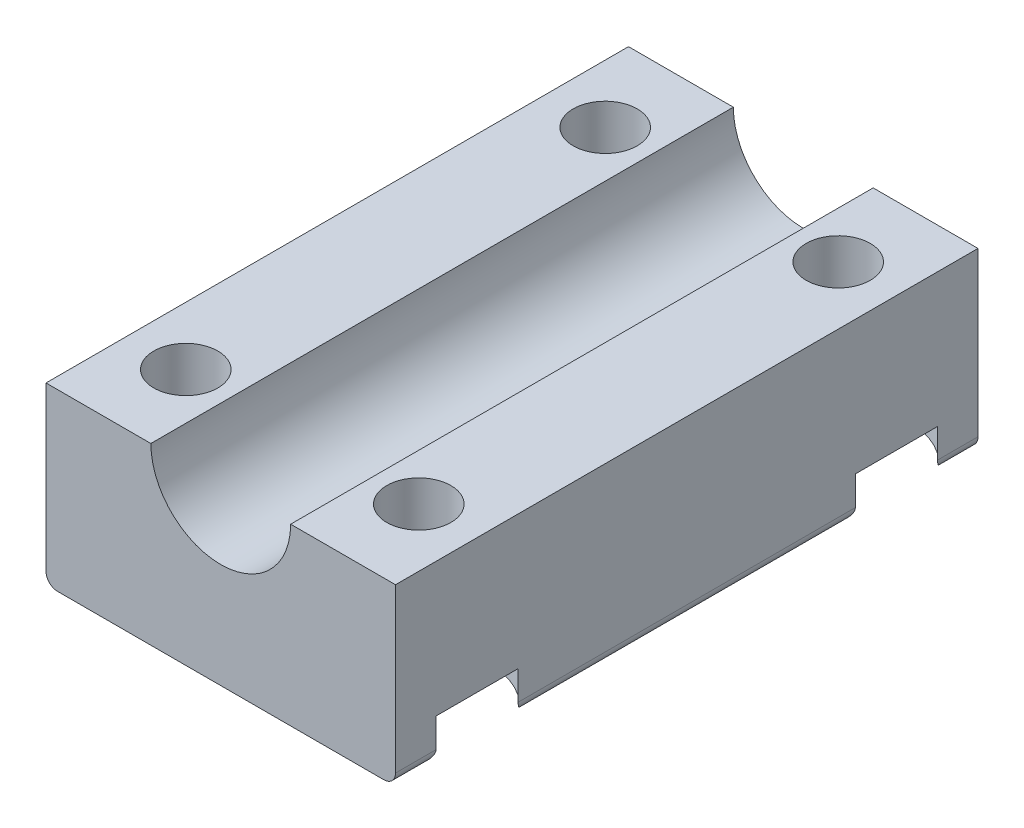
SolidWorks part; units mm, degrees
material "Alloy Steel"
ref_plane "Front Plane" through (0, 0, 0) normal (0, 0, 1) x (1, 0, 0)
ref_plane "Top Plane" through (0, 0, 0) normal (0, 1, 0) x (1, 0, 0)
ref_plane "Right Plane" through (0, 0, 0) normal (1, 0, 0) x (0, 0, -1)
sketch "Sketch1" plane through (0, 0, 0) normal (0, 0, 1) x (1, 0, 0)
  line L0 (6, 7.5) -> (15, 7.5)
  line L1 (-14, -7.5) -> (14, -7.5)
  line L2 (-15, -6.5) -> (-15, 7.5)
  line L3 (-15, 7.5) -> (-6, 7.5)
  line L4 (15, -6.5) -> (15, 7.5)
  line L5 (-15, -7.5) -> (15, 7.5) construction
  line L6 (-15, 7.5) -> (15, -7.5) construction
  arc A0 (-6, 7.5) -> (6, 7.5) centre (0, 7.5) ccw
  arc A1 (14, -7.5) -> (15, -6.5) centre (14, -6.5) ccw
  arc A2 (-14, -7.5) -> (-15, -6.5) centre (-14, -6.5) cw
  point P0 (0, 0)
  point P9 (0, 1.5)
  point P10 (0, 0)
  dimension "D3" = 6
  dimension "D4" = 1
  dimension "D1" = 15
  dimension "D2" = 30
extrude "Boss-Extrude2" add sketch "Sketch1" along normal mid plane 50
sketch "Sketch2" plane through (0, -7.5, 0) normal (0, -1, 0) x (1, 0, 0)
  line L0 (4.7581, 0) -> (-2.7583, 0) construction
  line L1 (0, 4.7237) -> (0, -3.4824) construction
  circle A0 centre (10, 18) radius 6.12
  circle A1 centre (10, 18) radius 2.75
  circle A2 centre (10, -18) radius 6.12
  circle A3 centre (10, -18) radius 2.75
  circle A4 centre (-10, -18) radius 2.75
  circle A5 centre (-10, -18) radius 6.12
  circle A6 centre (-10, 18) radius 6.12
  circle A7 centre (-10, 18) radius 2.75
  point P0 (10, 18)
  line M4 (14, -25) -> (14, 25)
  line M6 (-14, 25) -> (-14, -25)
  dimension "D2" = 12.24
  dimension "D4" = 5.5
  dimension "D1" = 10
  dimension "D3" = 18
extrude "Cut-Extrude1" cut sketch "Sketch2" against normal blind 3.5 contours A7 | A6 A7 M6 | A0 A1 M4 | A0 M4 | A6 M6 | A5 A4 M6 | A5 M6 | A4 | A2 A3 M4 | A3 | A2 M4 | A1 region at (14.862, -7.5, 18) region at (14.862, -7.5, -18) region at (13.8412, -7.5, -18) region at (13.8412, -7.5, 18) region at (10, -7.5, 18) region at (10, -7.5, -18) region at (-10, -7.5, -18) region at (-7.5191, -7.5, -23.4204) region at (-14.862, -7.5, 18) region at (-13.8412, -7.5, 18) region at (-14.862, -7.5, -18) region at (-10, -7.5, 18)
extrude "Cut-Extrude2" cut sketch "Sketch2<3>" against normal through all contours A7 | A1 | A3 | A4 region at (10, -7.5, 18) region at (10, -7.5, -18) region at (-10, -7.5, -18) region at (-10, -7.5, 18)
sketch "Sketch2<3>" plane through (0, -7.5, 0) normal (0, -1, 0) x (1, 0, 0) same geometry as "Sketch2"
